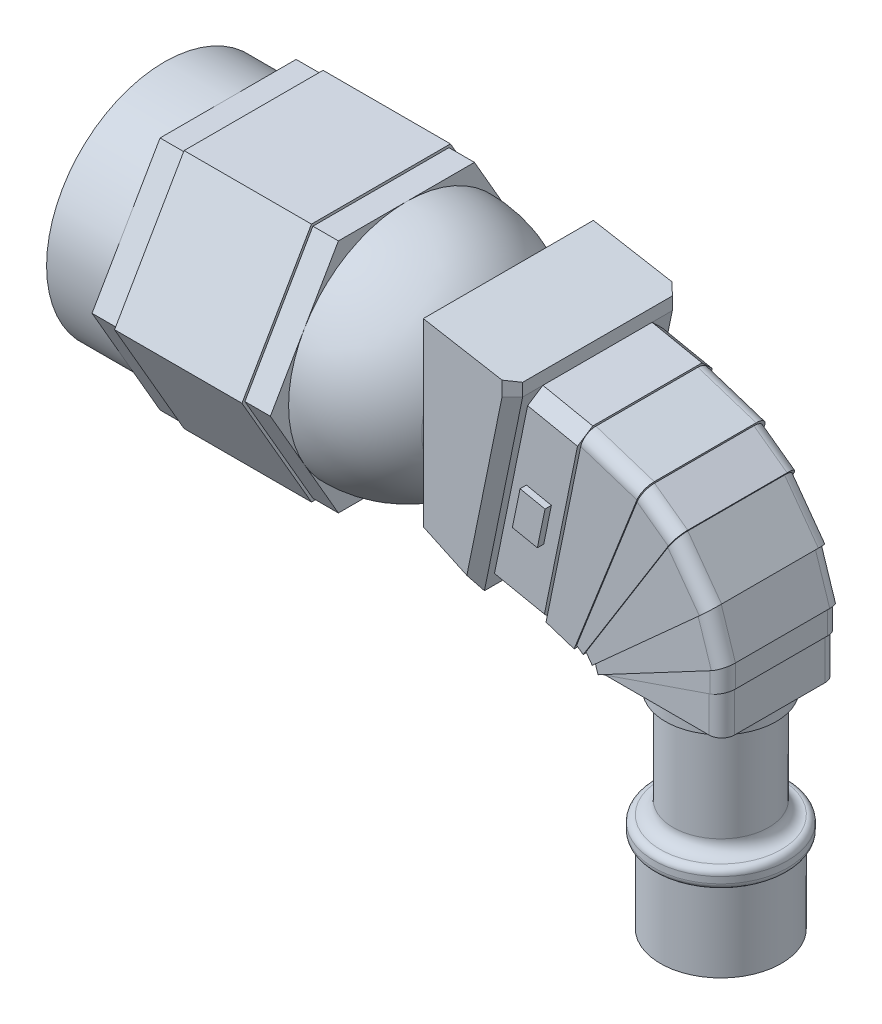
SolidWorks part; units mm, degrees
ref_plane "Front Plane" through (0, 0, 0) normal (0, 0, 1) x (1, 0, 0)
ref_plane "Top Plane" through (0, 0, 0) normal (0, 1, 0) x (1, 0, 0)
ref_plane "Right Plane" through (0, 0, 0) normal (1, 0, 0) x (0, 0, -1)
sketch "Sketch1" plane through (0, 0, 0) normal (1, 0, 0) x (0, 0, -1)
  circle A0 centre (0, 0) radius 9.25
  dimension "D1" = 18.5
extrude "Boss-Extrude1" add sketch "Sketch1" along normal blind 5
sketch "Sketch2" plane through (5, 0, 0) normal (1, 0, 0) x (0, 0, -1)
  line L0 (0, 9.25) -> (0, 0) construction
  line L1 (5.3405, -9.25) -> (10.681, 0)
  line L2 (10.681, 0) -> (5.3405, 9.25)
  line L3 (5.3405, 9.25) -> (-5.3405, 9.25)
  line L4 (-5.3405, 9.25) -> (-10.681, 0)
  line L5 (-10.681, 0) -> (-5.3405, -9.25)
  line L6 (-5.3405, -9.25) -> (5.3405, -9.25)
  circle A0 centre (0, 0) radius 9.25 construction
  circle A1 centre (0, 0) radius 9.25 construction
extrude "Boss-Extrude2" add sketch "Sketch2" along normal blind 14
sketch "Sketch3" plane through (19, 0, 0) normal (1, 0, 0) x (0, 0, -1)
  line L12 (-5.456, -9.45) -> (5.456, -9.45)
  line L13 (5.456, -9.45) -> (10.9119, 0)
  line L14 (10.9119, 0) -> (5.456, 9.45)
  line L15 (5.456, 9.45) -> (-5.456, 9.45)
  line L16 (-5.456, 9.45) -> (-10.9119, 0)
  line L17 (-10.9119, 0) -> (-5.456, -9.45)
  line L18 (-5.456, -9.45) -> (5.456, -9.45)
  line L19 (5.456, -9.45) -> (10.9119, 0)
  line L20 (10.9119, 0) -> (5.456, 9.45)
  line L21 (5.456, 9.45) -> (-5.456, 9.45)
  line L22 (-5.456, 9.45) -> (-10.9119, 0)
  line L23 (-10.9119, 0) -> (-5.456, -9.45)
  dimension "D1" = 0.2
extrude "Boss-Extrude3" add sketch "Sketch3" along normal blind 5 and the other way blind 5 from offset 7 offset against normal yes
sketch "Sketch5" plane through (19, 0, 0) normal (1, 0, 0) x (0, 0, -1)
  line L0 (0, 9.25) -> (0, -9.25)
  line L1 (5.3405, 9.25) -> (-5.3405, 9.25) construction
  line L2 (-5.3405, -9.25) -> (5.3405, -9.25) construction
  arc A0 (0, 9.25) -> (0, -9.25) centre (0, 0) cw
revolve "Revolve1" add sketch "Sketch5" angle 180 about L0
sketch "Sketch6" plane through (19, 0, 0) normal (1, 0, 0) x (0, 0, -1)
  line L1 (6.6756, -6.403) -> (-6.6756, -6.403)
  line L2 (6.6756, -6.403) -> (6.6756, 6.403)
  line L3 (6.6756, 6.403) -> (-6.6756, 6.403)
  line L4 (-6.6756, -6.403) -> (-6.6756, 6.403)
  line L5 (6.6756, -6.403) -> (-6.6756, 6.403) construction
  line L6 (6.6756, 6.403) -> (-6.6756, -6.403) construction
  arc A0 (8.0107, 4.625) -> (0, 9.25) centre (0, 0) ccw construction
  point P0 (0, 0)
extrude "Boss-Extrude4" add sketch "Sketch6" along normal blind 4 from offset 8
draft "Draft4" type of draft neutral plane draft angle 25 faces to draft 1 face at (29, -6.403, 0) neutral plane through (27, 0, 0) neutral plane normal (-1, 0, 0) parameters "D1"=25
sketch "Sketch7" plane through (0, 0, -6.6756) normal (0, 0, -1) x (-1, 0, 0)
  line L0 (-31, 6.403) -> (-34, 6.403)
  line L2 (-34, 6.403) -> (-31, -8.2683)
  line L3 (-31, 6.403) -> (-31, -8.2683)
  dimension "D1" = 3
extrude "Boss-Extrude5" add sketch "Sketch7" against normal up to surface (13.3512 mm away) up to face at (29, -0.4663, 6.6756)
sketch "Sketch8" plane through (31.3787, -6.4163, 0) normal (0.9797, -0.2003, 0) x (0, 0, -1)
  line L0 (0, 13.0846) -> (0, -1.8902) construction
  line L1 (-6.6756, 13.0846) -> (6.6756, 13.0846) construction
  line L2 (-6.6756, -1.8902) -> (6.6756, -1.8902) construction
  line L3 (-4.2855, 13.0846) -> (-5.2855, 12.0846)
  line L4 (4.2855, -1.8902) -> (-4.2855, -1.8902)
  line L5 (5.2855, -0.8902) -> (5.2855, 12.0846)
  line L6 (4.2855, 13.0846) -> (-4.2855, 13.0846)
  line L7 (-5.2855, -0.8902) -> (-5.2855, 12.0846)
  line L8 (5.2855, -1.8902) -> (-5.2855, 13.0846) construction
  line L9 (5.2855, 13.0846) -> (-5.2855, -1.8902) construction
  line L10 (5.2855, 12.0846) -> (4.2855, 13.0846)
  line L11 (5.2855, -0.8902) -> (4.2855, -1.8902)
  line L12 (-4.2855, -1.8902) -> (-5.2855, -0.8902)
  point P6 (0, 5.5972)
extrude "Boss-Extrude6" add sketch "Sketch8" along normal blind 4
chamfer "Chamfer1" distance 0.8 angle 45 4 edges at (29, -7.3356, 6.6756) (32.5, -0.9326, 6.6756) (29, -7.3356, -6.6756) (32.5, -0.9326, -6.6756)
sketch "Sketch9" plane through (0, 0, 5.2855) normal (0, 0, 1) x (1, 0, 0)
  line L0 (35.7591, 5.0226) -> (34.386, -1.6924) construction
  line L1 (37.7186, 4.622) -> (35.1192, -8.0899) construction
  line L2 (37.7186, 4.622) -> (33.7997, 5.4233) construction
  line L3 (33.7068, -0.0225) -> (35.6663, -0.4231)
  line L4 (35.6663, -0.4231) -> (35.0652, -3.3623)
  line L5 (35.0652, -3.3623) -> (33.1058, -2.9616)
  line L6 (33.1058, -2.9616) -> (33.7068, -0.0225)
  line L7 (33.7068, -0.0225) -> (35.0652, -3.3623) construction
  line L9 (33.1058, -2.9616) -> (35.6663, -0.4231) construction
  point P6 (34.386, -1.6924)
  dimension "D1" = 3
  dimension "D2" = 2
extrude "Boss-Extrude7" add sketch "Sketch9" along normal blind 0.5
mirror "Mirror1" about plane through (0, 0, 0) normal (0, 0, 1) of "Boss-Extrude7"
sketch "Sketch10" plane through (0, 0, 0) normal (0, 0, 1) x (1, 0, 0)
  line L4 (37.8834, 5.4282) -> (42.458, 3.9418)
  line L5 (37.9189, 5.6017) -> (37.7186, 4.622) construction
  line L6 (42.458, 3.9418) -> (37.1661, -9.5776)
  line L7 (37.1661, -9.5776) -> (34.9615, -8.8613)
  line L8 (35.1192, -8.0899) -> (34.9189, -9.0696) construction
  line L9 (37.8834, 5.4282) -> (34.9615, -8.8613)
  line L10 (30.0917, 6.403) -> (37.4961, 6.403) construction
  line L11 (33.1834, 6.403) -> (27, 6.403) construction
  dimension "D1" = 18
extrude "Boss-Extrude8" add sketch "Sketch10" along normal blind 5 and the other way blind 5
sketch "Sketch11" plane through (0, 0, 0) normal (0, 0, 1) x (1, 0, 0)
  line L0 (42.3827, 3.7495) -> (44.9863, 1.858)
  line L2 (44.9863, 1.858) -> (37.7785, -9.7072)
  line L3 (37.7785, -9.7072) -> (37.2622, -9.332)
  line L5 (30.0917, 6.403) -> (33.1834, 6.403) construction
  line L6 (33.1834, 6.403) -> (27, 6.403) construction
  line L7 (33.1834, 6.403) -> (37.2606, 6.403) construction
  line L8 (42.3827, 3.7495) -> (37.2622, -9.332)
  line L9 (37.1661, -9.5776) -> (42.458, 3.9418) construction
  dimension "D1" = 36
extrude "Boss-Extrude9" add sketch "Sketch11" along normal blind 4.9 and the other way blind 4.9
sketch "Sketch12" plane through (0, 0, 0) normal (0, 0, 1) x (1, 0, 0)
  line L0 (37.9009, -9.5108) -> (44.8935, 1.7091)
  line L1 (37.7785, -9.7072) -> (44.9863, 1.858) construction
  line L2 (44.8935, 1.7091) -> (47.5434, -1.9381)
  line L3 (47.5434, -1.9381) -> (38.3892, -10.1829)
  line L4 (38.3892, -10.1829) -> (37.9009, -9.5108)
  line L5 (12, 9.45) -> (17, 9.45) construction
  line L6 (7, 9.45) -> (17, 9.45) construction
  line L7 (17, 9.45) -> (40.6433, 9.45) construction
  dimension "D1" = 54
  dimension "D2" = 0.1754
extrude "Boss-Extrude10" add sketch "Sketch12" along normal blind 4.8 and the other way blind 4.8
sketch "Sketch13" plane through (0, 0, 0) normal (0, 0, 1) x (1, 0, 0)
  line L0 (38.5361, -10.0507) -> (47.4157, -2.0531)
  line L1 (38.3892, -10.1829) -> (47.5434, -1.9381) construction
  line L2 (47.4157, -2.0531) -> (48.5342, -5.4957)
  line L3 (48.5342, -5.4957) -> (38.7456, -10.6953)
  line L4 (38.7456, -10.6953) -> (38.5361, -10.0507)
  line L5 (30.0917, 6.403) -> (33.1834, 6.403) construction
  line L6 (33.1834, 6.403) -> (27, 6.403) construction
  line L7 (33.1834, 6.403) -> (39.2516, 6.403) construction
  dimension "D1" = 72
  dimension "D2" = 0.1719
extrude "Boss-Extrude11" add sketch "Sketch13" along normal blind 4.7 and the other way blind 4.7
sketch "Sketch14" plane through (0, 0, 0) normal (0, 0, 1) x (1, 0, 0)
  line L0 (38.76, -10.6876) -> (48.4506, -5.5401)
  line L1 (38.7456, -10.6953) -> (48.5342, -5.4957) construction
  line L2 (48.4506, -5.5401) -> (48.4506, -7.3553)
  line L3 (48.4506, -7.3553) -> (38.76, -10.6876)
  line L4 (12, 9.45) -> (17, 9.45) construction
  line L5 (7, 9.45) -> (17, 9.45) construction
  line L6 (17, 9.45) -> (41.1677, 9.45) construction
  dimension "D1" = 9
  dimension "D2" = 0.0947
extrude "Boss-Extrude12" add sketch "Sketch14" along normal blind 4.6 and the other way blind 4.6
sketch "Sketch15" plane through (0, 0, 0) normal (0, 0, 1) x (1, 0, 0)
  line L0 (48.3085, -7.4041) -> (39.0618, -10.5839)
  line L1 (38.76, -10.6876) -> (48.4506, -7.3553) construction
  line L2 (39.0618, -10.5839) -> (48.3085, -10.5839)
  line L3 (48.3085, -10.5839) -> (48.3085, -7.4041)
  dimension "D1" = 0.1503
extrude "Boss-Extrude13" add sketch "Sketch15" along normal blind 4.55 and the other way blind 4.55
fillet "Fillet1" radius 1 12 edges at (40.1707, 4.685, -5) (40.1707, 4.685, 5) (43.6845, 2.8037, -4.9) (43.6845, 2.8037, 4.9) (46.2185, -0.1145, 4.8) (46.2185, -0.1145, -4.8) (47.975, -3.7744, -4.7) (47.975, -3.7744, 4.7) (48.4506, -6.4477, -4.6) (48.4506, -6.4477, 4.6) (48.3085, -8.994, -4.55) (48.3085, -8.994, 4.55)
sketch "Sketch16" plane through (0, -10.5839, 0) normal (0, -1, 0) x (1, 0, 0)
  line L0 (39.0618, 0) -> (48.3085, 0) construction
  line L3 (48.3085, -3.55) -> (48.3085, 3.55) construction
  line L4 (39.0618, -4.55) -> (39.0618, 4.55) construction
  circle A0 centre (43.6851, 0) radius 4.35
  dimension "D1" = 8.7
extrude "Boss-Extrude14" add sketch "Sketch16" along normal blind 1
sketch "Sketch17" plane through (0, -11.5839, 0) normal (0, -1, 0) x (1, 0, 0)
  circle A3 centre (43.6851, 0) radius 3.75
  dimension "D1" = 7.5
extrude "Boss-Extrude15" add sketch "Sketch17" along normal blind 8.5
sketch "Sketch18" plane through (0, -20.0839, 0) normal (0, -1, 0) x (1, 0, 0)
  circle A3 centre (43.6851, 0) radius 5.25
  dimension "D1" = 10.5
extrude "Boss-Extrude16" add sketch "Sketch18" along normal blind 1.5
sketch "Sketch19" plane through (0, -21.5839, 0) normal (0, -1, 0) x (1, 0, 0)
  circle A2 centre (43.6851, 0) radius 4.75
  circle A3 centre (43.6851, 0) radius 4.75
  dimension "D1" = 0.5
extrude "Boss-Extrude17" add sketch "Sketch19" along normal blind 0.25
sketch "Sketch21" plane through (0, -21.8339, 0) normal (0, -1, 0) x (1, 0, 0)
  circle A3 centre (43.6851, 0) radius 4.75
  dimension "D1" = 9.5
extrude "Boss-Extrude18" add sketch "Sketch21" along normal blind 6
sketch "Sketch22" plane through (0, -27.8339, 0) normal (0, -1, 0) x (1, 0, 0)
  circle A3 centre (43.6851, 0) radius 3.5
  dimension "D1" = 7
extrude "Boss-Extrude19" add sketch "Sketch22" along normal blind 1
chamfer "Chamfer3" distance 0.25 angle 45 1 edges at (43.6851, -28.8339, -3.5)
fillet "Fillet2" radius 1 1 edges at (43.6851, -20.0839, -3.75)
sketch "Sketch23" plane through (0, 6.403, 0) normal (0, 1, 0) x (1, 0, 0)
  line L8 (27, -6.6756) -> (33.1834, -6.6756)
  line L9 (33.1834, -6.6756) -> (34, -5.8756)
  line L10 (34, -5.8756) -> (34, -4.2855)
  line L11 (34, -4.2855) -> (34, 4.2855)
  line L12 (34, 4.2855) -> (34, 5.8756)
  line L13 (34, 5.8756) -> (33.1834, 6.6756)
  line L14 (33.1834, 6.6756) -> (27, 6.6756)
  line L15 (27, 6.6756) -> (27, -6.6756)
  line L16 (27, -6.6756) -> (33.1834, -6.6756)
  line L17 (33.1834, -6.6756) -> (34, -5.8756)
  line L18 (34, -5.8756) -> (34, -4.2855)
  line L19 (34, -4.2855) -> (34, 4.2855)
  line L20 (34, 4.2855) -> (34, 5.8756)
  line L21 (34, 5.8756) -> (33.1834, 6.6756)
  line L22 (33.1834, 6.6756) -> (27, 6.6756)
  line L23 (27, 6.6756) -> (27, -6.6756)
  dimension "D1" = 0
extrude "Boss-Extrude20" add sketch "Sketch23" along normal blind 1
draft "Draft8" type of draft neutral plane draft angle 10 faces to draft 1 face at (31.3945, 7.403, 0) neutral plane through (34, 7.403, -4.2855) neutral plane normal (1, 0, 0) parameters "D1"=10
fillet "Fillet3" radius 0.5 1 edges at (27, 0, -4.6435)
fillet "Fillet4" radius 0.5 2 edges at (43.6851, -21.5839, -5.25) (43.6851, -20.0839, -5.25)
equation "\"ArmHex1\"=10"
equation "\"Arm\"=4"
